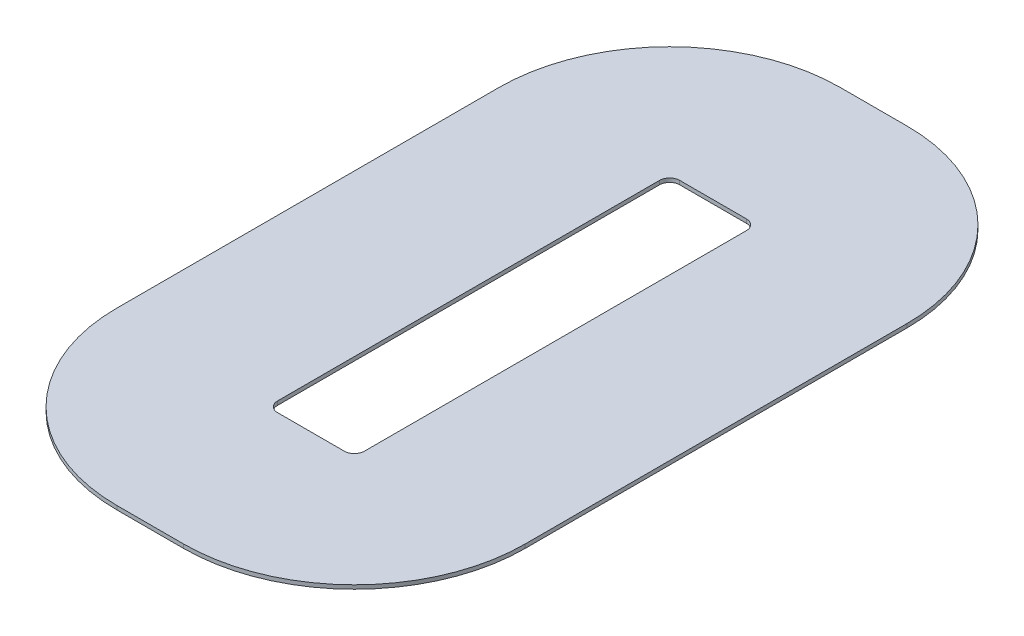
SolidWorks part; units mm, degrees
ref_plane "Спереди" through (0, 0, 0) normal (0, 0, 1) x (1, 0, 0)
ref_plane "Сверху" through (0, 0, 0) normal (0, 1, 0) x (1, 0, 0)
ref_plane "Справа" through (0, 0, 0) normal (1, 0, 0) x (0, 0, -1)
sketch "Эскиз1" plane through (0, 0, 0) normal (0, 1, 0) x (1, 0, 0)
  line L0 (-24.45, 0) -> (24.45, 0) construction
  line L5 (0, -44.25) -> (0, 44.25) construction
  line L7 (-4.3, 25.9) -> (4.3, 25.9)
  line L8 (-5.6, 24.6) -> (-5.6, -24.6)
  line L9 (-4.3, -25.9) -> (4.3, -25.9)
  line L10 (5.6, 24.6) -> (5.6, -24.6)
  line L11 (-4.3, 46.6) -> (4.3, 46.6)
  line L12 (-26.3, 24.6) -> (-26.3, -24.6)
  line L13 (-4.3, -46.6) -> (4.3, -46.6)
  line L14 (26.3, 24.6) -> (26.3, -24.6)
  arc A0 (4.3, 46.6) -> (26.3, 24.6) centre (4.3, 24.6) cw
  arc A1 (-4.3, 46.6) -> (-26.3, 24.6) centre (-4.3, 24.6) ccw
  arc A2 (4.3, -46.6) -> (26.3, -24.6) centre (4.3, -24.6) ccw
  arc A3 (-26.3, -24.6) -> (-4.3, -46.6) centre (-4.3, -24.6) ccw
  arc A4 (4.3, -25.9) -> (5.6, -24.6) centre (4.3, -24.6) ccw
  arc A5 (-5.6, -24.6) -> (-4.3, -25.9) centre (-4.3, -24.6) ccw
  arc A6 (4.3, 25.9) -> (5.6, 24.6) centre (4.3, 24.6) cw
  arc A7 (-4.3, 25.9) -> (-5.6, 24.6) centre (-4.3, 24.6) ccw
  dimension "D1" = 22
  dimension "D2" = 1.3
base flange "Базовая кромка1" sketch "Эскиз1" thickness 0.5 reverse thickness direction no parameters "D1"=0.7366
sketch "Сгиб-Линии1" plane through (0, 0, 0) normal (0, 1, 0) x (1, 0, 0)
sketch "Граничная рамка1" plane through (0, 0, 0) normal (0, 1, 0) x (1, 0, 0)
sheet metal parameters "Листовой металл3" thickness 0.5 parameters "D1"=0.7366
flat pattern "Развертка3" [suppressed]
sketch "Сгиб-Линии2" plane through (0, 0, 0) normal (0, 1, 0) x (1, 0, 0)
sketch "Граничная рамка2" [suppressed] plane through (0, 0, 0) normal (0, 1, 0) x (1, 0, 0)
